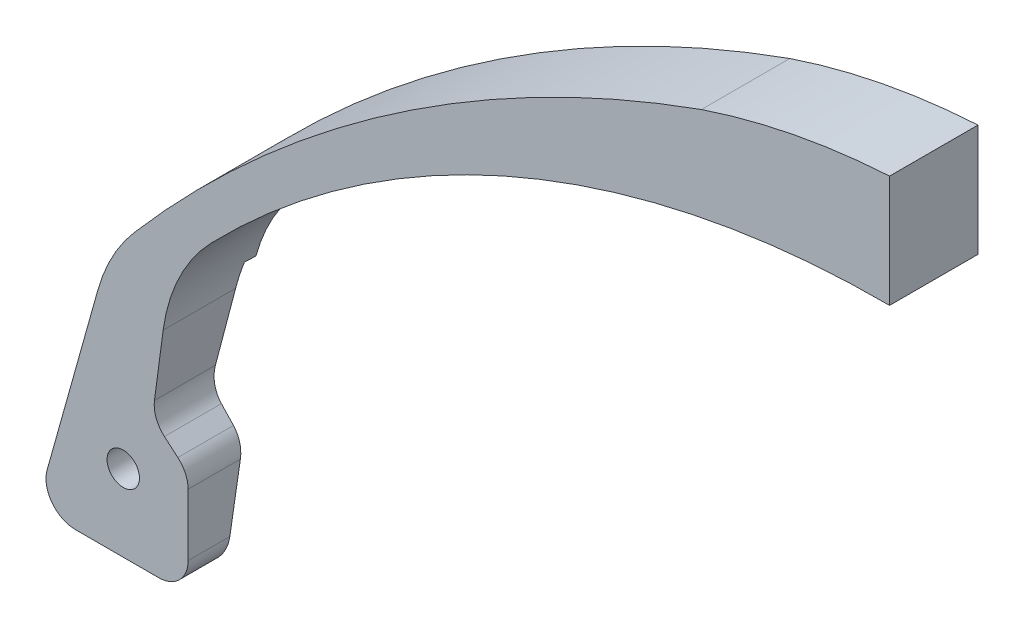
SolidWorks part; units mm, degrees
ref_plane "Plan de face" through (0, 0, 0) normal (0, 0, 1) x (1, 0, 0)
ref_plane "Plan de dessus" through (0, 0, 0) normal (0, 1, 0) x (1, 0, 0)
ref_plane "Plan de droite" through (0, 0, 0) normal (1, 0, 0) x (0, 0, -1)
sketch "Esquisse1" plane through (0, 0, 0) normal (0, 0, 1) x (1, 0, 0)
  line L0 (0, 108) -> (0, 0)
  line L1 (0, 0) -> (-130, 0)
  dimension "D1" = 108
  dimension "D2" = 130
ref_axis "Axe1" through (0, 108, 0) along (0, -1, 0)
ref_axis "Axe2" through (0, 0, 0) along (-1, 0, 0)
sketch "Esquisse3" plane through (0, 0, 0) normal (0, 0, 1) x (1, 0, 0)
  line L0 (0, 108) -> (0, 0) construction
  line L1 (0, 0) -> (-130, 0) construction
  point P0 (-119, 35)
  dimension "D1" = 119
  dimension "D2" = 35
sketch "Esquisse2" plane through (0, 0, 0) normal (0, 0, 1) x (1, 0, 0)
  line L0 (0, 108) -> (0, 0) construction
  line L1 (-125.0643, 10) -> (-122, 33)
  line L2 (0, 0) -> (-130, 0) construction
  line L3 (-125.0643, 10) -> (-119, 4.7823)
  line L4 (-119, 4.7823) -> (-119, -13)
  line L5 (-119, -13) -> (-144.7, -13)
  line L6 (-144.7, -13) -> (-132.5643, 30.3327)
  line L7 (0, 108) -> (0, 89)
  circle A0 centre (-130, 0) radius 2.75
  arc A1 (-31.9184, 101.8188) -> (-132.5643, 30.3327) centre (45.2497, -113.4201) ccw
  arc A3 (0, 89) -> (-122, 33) centre (-0.8451, -70.0518) ccw
  arc A5 (-31.9184, 101.8188) -> (0, 108) centre (7.063, -13.9727) cw
  dimension "D1" = 5.5
  dimension "D2" = 89
  dimension "D3" = 10
  dimension "D4" = 119
  dimension "D5" = 25.7
  dimension "D6" = 122
  dimension "D7" = 8
  dimension "D8" = 13
  dimension "D9" = 33
  dimension "D10" = 132.5643
extrude "Boss.-Extru.1" add sketch "Esquisse2" along normal blind 15
sketch "Esquisse5" plane through (-130.8003, 36.6317, 0) normal (-0.9629, 0.2697, 0) x (0, 0, 1)
  line L1 (0, -51.5413) -> (10, -51.5413)
  line L7 (15, -51.5413) -> (0, -51.5413) construction
  line L8 (10, -51.5413) -> (2, -6.4184)
  line L9 (2, -6.4184) -> (0, -6.5413)
  line L10 (0, -6.5413) -> (0, -51.5413)
  dimension "D1" = 5
  dimension "D2" = 13
extrude "Enlèv. mat.-Extru.1" cut sketch "Esquisse5" against normal blind 36
ref_plane "Plan1" through (0, 108, 0) normal (0, 1, 0) x (1, 0, 0)
fillet "Congé1" radius 30 1 edges at (-132.5643, 30.3327, 8.5109)
fillet "Congé2" radius 30 1 edges at (-122, 33, 7.5)
fillet "Congé3" radius 5 1 edges at (-125.0643, 10, 10.0672)
fillet "Congé4" radius 5 1 edges at (-119, 4.7823, 10.3677)
fillet "Congé5" radius 5 1 edges at (-119, -13, 11.8856)
fillet "Congé6" radius 5 1 edges at (-144.7, -13, 12.5)
